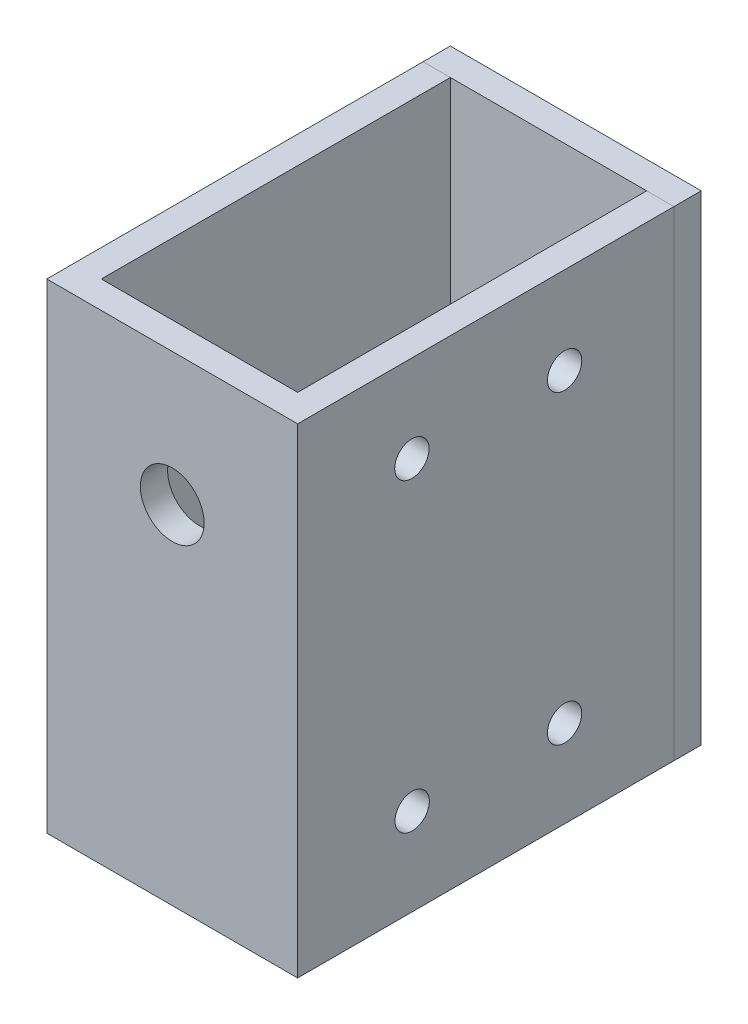
SolidWorks part; units mm, degrees
ref_plane "Front Plane" through (0, 0, 0) normal (0, 0, 1) x (1, 0, 0)
ref_plane "Top Plane" through (0, 0, 0) normal (0, 1, 0) x (1, 0, 0)
ref_plane "Right Plane" through (0, 0, 0) normal (1, 0, 0) x (0, 0, -1)
sketch "Sketch1" plane through (0, 0, 0) normal (0, 0, 1) x (1, 0, 0)
  line L0 (0, 0) -> (0, 55.88)
  line L1 (3.175, 55.88) -> (3.175, 3.175)
  line L2 (3.175, 3.175) -> (26.035, 3.175)
  line L3 (26.035, 3.175) -> (26.035, 55.88)
  line L4 (26.035, 55.88) -> (29.21, 55.88)
  line L5 (29.21, 55.88) -> (29.21, 0)
  line L6 (29.21, 0) -> (0, 0)
  line L7 (0, 55.88) -> (3.175, 55.88)
  dimension "D1" = 55.88
  dimension "D2" = 55.88
  dimension "D3" = 3.175
  dimension "D4" = 3.175
  dimension "D5" = 52.705
  dimension "D6" = 22.86
extrude "Boss-Extrude1" add sketch "Sketch1" along normal blind 40.64
ref_plane "Plane1" through (0, 0, 0) normal (0, 0, -1) x (-1, 0, 0)
sketch "Sketch2" plane through (0, 0, 0) normal (0, 0, -1) x (-1, 0, 0)
  line L0 (-29.21, 55.88) -> (-29.21, 0)
  line L1 (-29.21, 0) -> (0, 0)
  line L2 (0, 0) -> (0, 55.88)
  line L3 (0, 55.88) -> (-29.21, 55.88)
extrude "Boss-Extrude2" add sketch "Sketch2" along normal blind 3.175 separate body
ref_plane "Plane2" through (0, 0, 40.64) normal (0, 0, 1) x (1, 0, 0)
sketch "Sketch3" plane through (0, 0, 40.64) normal (0, 0, 1) x (1, 0, 0)
  line L0 (0, 55.88) -> (0, 0)
  line L1 (0, 0) -> (29.21, 0)
  line L2 (29.21, 0) -> (29.21, 55.88)
  line L3 (29.21, 55.88) -> (0, 55.88)
  line L4 (14.605, 55.88) -> (14.605, 0) construction
  line L5 (14.605, 55.88) -> (14.605, 40.4263) construction
  circle A0 centre (14.605, 40.4263) radius 3.7124
extrude "Boss-Extrude3" add sketch "Sketch3" along normal blind 3.175
ref_plane "Plane13" through (29.21, 0, 0) normal (1, 0, 0) x (0, 0, -1)
sketch "Sketch4" plane through (29.21, 0, 0) normal (1, 0, 0) x (0, 0, -1)
  line L0 (-43.815, 55.88) -> (3.175, 55.88) construction
  line L1 (3.175, 55.88) -> (-20.32, 55.88) construction
  line L2 (-20.32, 55.88) -> (-20.32, 0) construction
  line L3 (-43.815, 0) -> (0, 0) construction
  line L5 (-40.64, 55) -> (-40.64, -55) construction
  line L6 (0, -16.0655) -> (0, 16.0655) construction
  line L11 (0, 55.88) -> (-20.32, 55.88) construction
  line L12 (-10.16, 55.88) -> (-10.16, 0) construction
  line L13 (-20.32, 55.88) -> (-40.64, 55.88) construction
  line L14 (-40.64, 55.88) -> (-30.48, 55.88) construction
  line L15 (-30.48, 55.88) -> (-30.48, 0) construction
  line L16 (-40.64, 45.72) -> (0, 45.72) construction
  line L17 (0, 45.72) -> (0, 10.16) construction
  line L18 (0, 10.16) -> (-40.64, 10.16) construction
  line L19 (-10.16, 55.88) -> (0, 55.88)
  line L20 (0, 55.88) -> (0, 45.72)
  line L21 (0, 10.16) -> (0, 0)
  line L22 (-30.5127, 45.72) -> (-12.7327, 45.72) construction
  line L23 (-12.7327, 45.72) -> (-12.7327, 10.16) construction
  circle A1 centre (-12.7327, 45.72) radius 2
  circle A2 centre (-30.48, 10.16) radius 2
  circle A3 centre (-12.7327, 10.16) radius 2
  circle A4 centre (-30.5127, 45.72) radius 2
  point P23 (-30.5127, 45.72)
  point P28 (-12.7327, 45.72)
  point P29 (-12.7327, 10.16)
  point P30 (-30.48, 10.16)
  dimension "D6" = 17.78
  dimension "D1" = 10.16
  dimension "D2" = 10.16
  dimension "D3" = 10.16
  dimension "D4" = 10.16
  dimension "D5" = 10.16
extrude "Cut-Extrude1" cut sketch "Sketch4" against normal blind 3.175 contours A1 | A3 | A2 | A4 region at (29.21, 45.72, 12.7327) region at (29.21, 10.16, 30.48) region at (29.21, 10.16, 12.7327)
